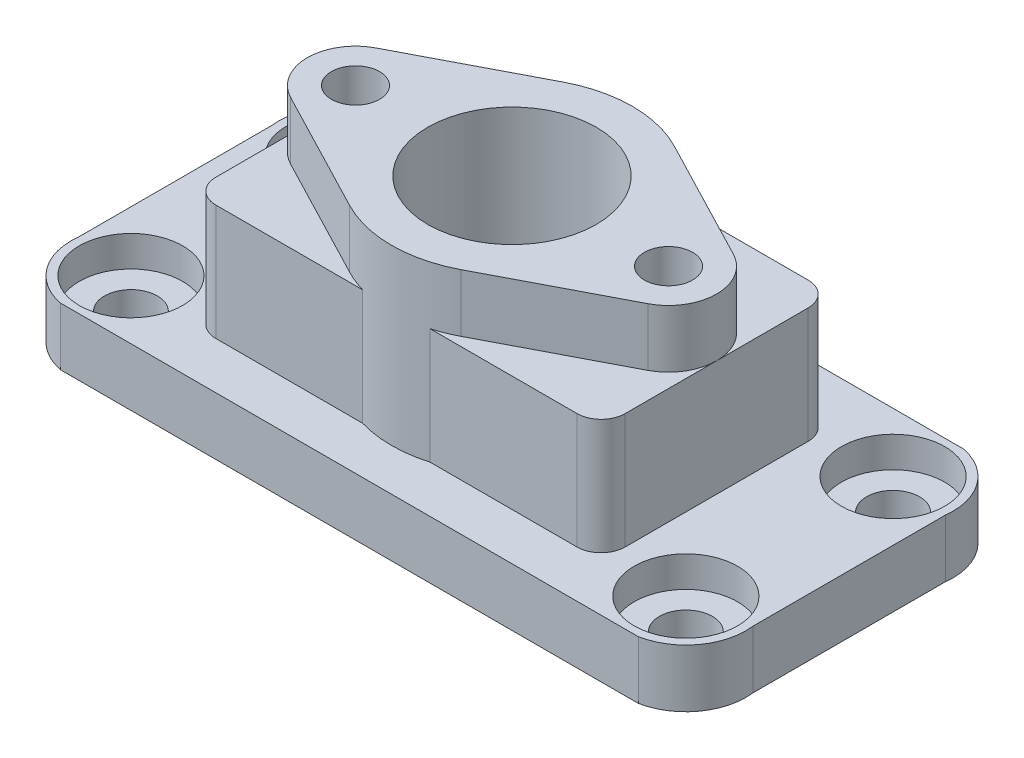
SolidWorks part; units mm, degrees
ref_plane "Front Plane" through (0, 0, 0) normal (0, 0, 1) x (1, 0, 0)
ref_plane "Top Plane" through (0, 0, 0) normal (0, 1, 0) x (1, 0, 0)
ref_plane "Right Plane" through (0, 0, 0) normal (1, 0, 0) x (0, 0, -1)
sketch "Sketch1" plane through (0, 0, 0) normal (0, 1, 0) x (1, 0, 0)
  line L0 (-60, -33.7577) -> (60, -33.7577)
  line L1 (60, -33.7577) -> (60, 33.7577) construction
  line L2 (60, 33.7577) -> (-60, 33.7577)
  line L3 (-60, 33.7577) -> (-60, -33.7577) construction
  line L4 (0, -33.7577) -> (0, 33.7577) construction
  line L5 (0, 33.7577) -> (-60, 0) construction
  line L6 (-60, 0) -> (60, 0) construction
  line L7 (-70, 20) -> (-70, -20)
  line L8 (70, 20) -> (70, -20)
  arc A1 (-60, -33.7577) -> (-70, -20) centre (-57.6158, -21.5116) cw
  arc A2 (-60, 33.7577) -> (-70, 20) centre (-57.6158, 21.5116) ccw
  arc A3 (60, -33.7577) -> (70, -20) centre (57.6158, -21.5116) ccw
  arc A4 (60, 33.7577) -> (70, 20) centre (57.6158, 21.5116) cw
  point P4 (0, -33.7577)
  point P8 (0, 0)
  point P11 (0, 33.7577)
  point P16 (-67.7076, 28.847)
  dimension "D1" = 120
  dimension "D2" = 40
  dimension "D3" = 70
extrude "Boss-Extrude1" add sketch "Sketch1" along normal blind 12
sketch "Sketch2" plane through (0, 12, 0) normal (0, 1, 0) x (1, 0, 0)
  arc A1 (-60, 33.7577) -> (-70, 20) centre (-57.6158, 21.5116) ccw construction
  arc A2 (-70, -20) -> (-60, -33.7577) centre (-57.6158, -21.5116) ccw construction
  arc A3 (60, -33.7577) -> (70, -20) centre (57.6158, -21.5116) ccw construction
  arc A4 (70, 20) -> (60, 33.7577) centre (57.6158, 21.5116) ccw construction
  point P0 (-57.6158, 21.5116)
  point P1 (-57.6158, -21.5116)
  point P2 (57.6158, -21.5116)
  point P3 (57.6158, 21.5116)
  point P4 (0, 0)
  point P8 (0, 0)
  point P9 (0, 0)
hole_wizard "CBORE for M10 Hex Head Cap Screw1" positions "3DSketch1" profile "Sketch3" counterbore size "M10" standard "ISO" end condition through all
sketch3d "3DSketch1"
  point P0 (-57.6158, 12, -21.5116)
  point P3 (-57.6158, 12, 21.5116)
  point P6 (57.6158, 12, 21.5116)
  point P9 (57.6158, 12, -21.5116)
sketch "Sketch3" plane through (-57.6158, 12, -21.5116) normal (1, 0, 0) x (0, 0, 1)
  line L0 (0, 0) -> (0, 12)
  line L1 (0, 12) -> (5.5, 12)
  line L3 (5.5, 12) -> (5.5, 6.4)
  line L4 (5.5, 6.4) -> (10.7375, 6.4)
  line L5 (10.7375, 6.4) -> (10.7375, 0)
  line L7 (10.7375, 0) -> (0, 0)
  line L11 (0, -6.35) -> (0, 107.95) construction
  dimension "Thru Hole Dia." = 11
  dimension "Thru Hole Depth" = 12
  dimension "C'Bore Dia." = 21.475
  dimension "C'Bore Depth" = 6.4
sketch "Sketch4" plane through (0, 12, 0) normal (0, 1, 0) x (1, 0, 0)
  line L0 (42.5, 0) -> (-42.5, 0) construction
  line L1 (-37.5, 24) -> (37.5, 24)
  line L2 (-42.5, 19) -> (-42.5, -19)
  line L3 (-37.5, -24) -> (37.5, -24)
  line L4 (42.5, 19) -> (42.5, -19)
  line L5 (-42.5, 24) -> (42.5, -24) construction
  line L6 (-42.5, -24) -> (42.5, 24) construction
  line L7 (-37.1154, -8.8712) -> (-11.5385, -22.178)
  line L8 (0, -33.7577) -> (0, 33.7577) construction
  line L9 (0, -33.7577) -> (0, 33.7577) construction
  line L10 (37.1154, -8.8712) -> (11.5385, -22.178)
  line L11 (-37.1154, 8.8712) -> (-11.5385, 22.178)
  line L12 (37.1154, 8.8712) -> (11.5385, 22.178)
  arc A0 (37.5, -24) -> (42.5, -19) centre (37.5, -19) ccw
  arc A1 (37.5, 24) -> (42.5, 19) centre (37.5, 19) cw
  arc A2 (-37.5, 24) -> (-42.5, 19) centre (-37.5, 19) ccw
  arc A3 (-42.5, -19) -> (-37.5, -24) centre (-37.5, -19) ccw
  arc A4 (-37.1154, 8.8712) -> (-37.1154, -8.8712) centre (-32.5, 0) ccw
  arc A5 (37.1154, -8.8712) -> (37.1154, 8.8712) centre (32.5, 0) ccw
  circle A6 centre (-32.5, 0) radius 5
  circle A7 centre (32.5, 0) radius 5
  circle A8 centre (0, 0) radius 25
  circle A9 centre (0, 0) radius 17.5
  point P0 (0, 0)
  dimension "D1" = 5
  dimension "D4" = 20
  dimension "D5" = 10
  dimension "D6" = 50
  dimension "D7" = 35
  dimension "D2" = 75
  dimension "D3" = 48
extrude "Boss-Extrude3" add sketch "Sketch4" along normal blind 24 contours A8 L1 A2 L2 A4 L11 | A8 L7 A4 L2 A3 L3 | A8 L3 A0 L4 A5 L10 | A8 L12 A5 L4 A1 L1 | L3 A8 L1 A9 | L1 A8 | A8 L11 A4 L7 A6 | A8 L10 A5 L12 A7 | A7 | A6 | L3 A8 region at (-30.9978, 12, -17.6988) region at (0, 12, -24.4007) region at (0, 12, -23.3069) region at (30.9978, 12, -17.6988) region at (-25.5409, 12, 0) region at (-30.9978, 12, 17.6988) region at (24.0773, 12, -15.0447) region at (0, 12, 24.4007) region at (30.9978, 12, 17.6988) region at (-32.5, 12, 0) region at (32.5, 12, 0)
sketch "Sketch7" plane through (0, 36, 0) normal (0, 1, 0) x (1, 0, 0)
  line L0 (-37.1154, 8.8712) -> (-11.5385, 22.178) construction
  line L1 (-37.1154, -8.8712) -> (-11.5385, -22.178) construction
  line L2 (37.1154, -8.8712) -> (11.5385, -22.178) construction
  line L3 (37.1154, 8.8712) -> (11.5385, 22.178) construction
  line L6 (42.5, -19) -> (42.5, 19)
  line L7 (37.5, 24) -> (7, 24)
  line L8 (-7, 24) -> (-37.5, 24)
  line L9 (-42.5, 19) -> (-42.5, -19)
  line L10 (-37.5, -24) -> (-7, -24)
  line L11 (7, -24) -> (37.5, -24)
  line L24 (-37.1154, 8.8712) -> (-11.5385, 22.178)
  line L25 (-37.1154, -8.8712) -> (-11.5385, -22.178)
  line L26 (37.1154, -8.8712) -> (11.5385, -22.178)
  line L27 (37.1154, 8.8712) -> (11.5385, 22.178)
  arc A0 (-37.1154, 8.8712) -> (-37.1154, -8.8712) centre (-32.5, 0) ccw construction
  circle A1 centre (0, 0) radius 17.5
  circle A2 centre (0, 0) radius 17.5
  circle A3 centre (0, 0) radius 25
  circle A4 centre (0, 0) radius 25
  circle A5 centre (32.5, 0) radius 5
  arc A6 (42.5, 19) -> (37.5, 24) centre (37.5, 19) ccw
  arc A7 (7, 24) -> (-7, 24) centre (0, 0) ccw
  arc A8 (-37.5, 24) -> (-42.5, 19) centre (-37.5, 19) ccw
  arc A9 (-42.5, -19) -> (-37.5, -24) centre (-37.5, -19) ccw
  arc A10 (-7, -24) -> (7, -24) centre (0, 0) ccw
  arc A11 (37.5, -24) -> (42.5, -19) centre (37.5, -19) ccw
  arc A13 (7, 24) -> (-7, 24) centre (0, 0) ccw
  arc A16 (-7, -24) -> (7, -24) centre (0, 0) ccw
  circle A18 centre (32.5, 0) radius 5
  circle A19 centre (-32.5, 0) radius 5
  circle A20 centre (-32.5, 0) radius 5
  arc A21 (37.1154, -8.8712) -> (37.1154, 8.8712) centre (32.5, 0) ccw construction
  arc A22 (-37.1154, 8.8712) -> (-37.1154, -8.8712) centre (-32.5, 0) ccw
  arc A23 (37.1154, -8.8712) -> (37.1154, 8.8712) centre (32.5, 0) ccw
  arc M28 (7, 24) -> (-7, 24) centre (0, 0) ccw
  arc M34 (-7, -24) -> (7, -24) centre (0, 0) ccw
  circle M37 centre (0, 0) radius 17.5
  dimension "D1" = 0
  dimension "D2" = 0
  dimension "D3" = 0
  dimension "D4" = 0
  dimension "D5" = 0
extrude "Boss-Extrude4" add sketch "Sketch7" along normal blind 12 contours L24 A22 L25 A4 A20 | L26 A23 L27 A4 A18 | A4 M34 M28 M37 region at (40.5861, 36, 4.9081) region at (0, 36, 24.2929) region at (-24.0773, 36, 15.0447)
sketch "Sketch8" plane through (0, 48, 0) normal (0, 1, 0) x (1, 0, 0)
  line L4 (-11.5385, 22.178) -> (-37.1154, 8.8712)
  line L5 (-37.1154, -8.8712) -> (-11.5385, -22.178)
  line L6 (11.5385, -22.178) -> (37.1154, -8.8712)
  line L7 (37.1154, 8.8712) -> (11.5385, 22.178)
  line L8 (-11.5385, 22.178) -> (-37.1154, 8.8712)
  line L9 (-37.1154, -8.8712) -> (-11.5385, -22.178)
  line L10 (11.5385, -22.178) -> (37.1154, -8.8712)
  line L11 (37.1154, 8.8712) -> (11.5385, 22.178)
  circle A0 centre (0, 0) radius 17.5 construction
  circle A1 centre (0, 0) radius 17.5
  circle A2 centre (32.5, 0) radius 5 construction
  circle A3 centre (32.5, 0) radius 5
  arc A4 (-37.1154, 8.8712) -> (-37.1154, -8.8712) centre (-32.5, 0) ccw
  arc A5 (-11.5385, -22.178) -> (11.5385, -22.178) centre (0, 0) ccw
  arc A6 (37.1154, -8.8712) -> (37.1154, 8.8712) centre (32.5, 0) ccw
  arc A7 (11.5385, 22.178) -> (-11.5385, 22.178) centre (0, 0) ccw
  arc A8 (-37.1154, 8.8712) -> (-37.1154, -8.8712) centre (-32.5, 0) ccw
  arc A9 (-11.5385, -22.178) -> (11.5385, -22.178) centre (0, 0) ccw
  arc A10 (37.1154, -8.8712) -> (37.1154, 8.8712) centre (32.5, 0) ccw
  arc A11 (11.5385, 22.178) -> (-11.5385, 22.178) centre (0, 0) ccw
  circle A12 centre (-32.5, 0) radius 5 construction
  circle A13 centre (-32.5, 0) radius 5
  circle M20 centre (0, 0) radius 17.5
  dimension "D1" = 0
extrude "Cut-Extrude2" cut sketch "Sketch8" against normal through all contours M20 | A13 | A3 region at (0, 48, 0)
